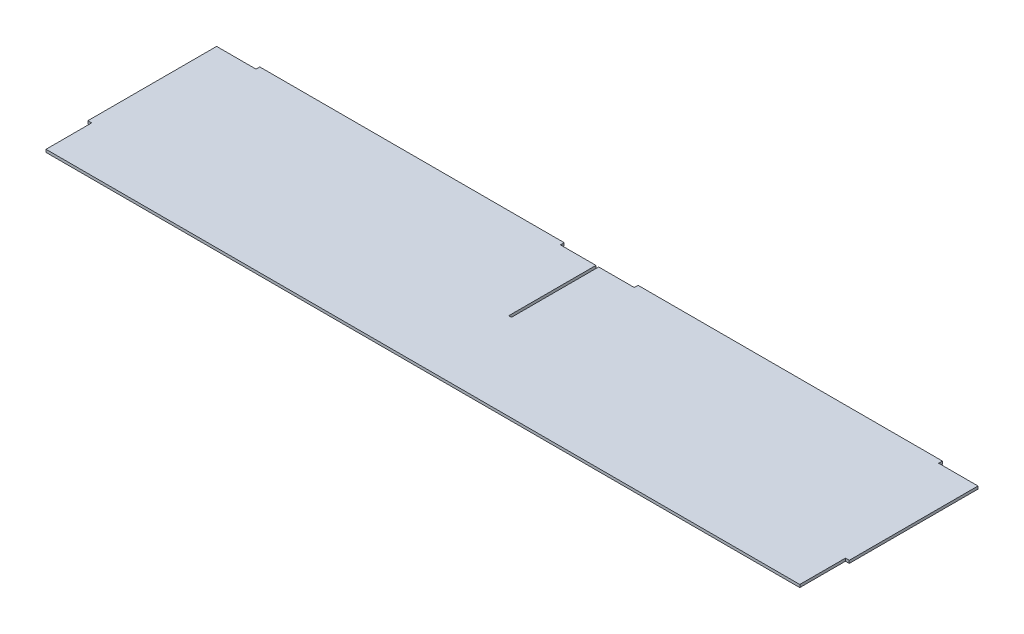
SolidWorks part; units mm, degrees
material "6061-T6 (SS)"
ref_plane "X-Y Datum" through (0, 0, 0) normal (0, 0, 1) x (1, 0, 0)
ref_plane "X-Z Datum" through (0, 0, 0) normal (0, 1, 0) x (1, 0, 0)
ref_plane "Y-Z Datum" through (0, 0, 0) normal (1, 0, 0) x (0, 0, -1)
sketch "Sketch1" plane through (0, 0, 0) normal (0, 1, 0) x (1, 0, 0)
  line L1 (-317.6778, 72.771) -> (317.6778, 72.771)
  line L2 (-317.6778, 72.771) -> (-317.6778, -72.771)
  line L3 (-317.6778, -72.771) -> (317.6778, -72.771)
  line L4 (317.6778, 72.771) -> (317.6778, -72.771)
  line L5 (-317.6778, 72.771) -> (317.6778, -72.771) construction
  line L6 (-317.6778, -72.771) -> (317.6778, 72.771) construction
  point P0 (0, 0)
  dimension "D1" = 635.3556
  dimension "D2" = 145.542
extrude "Boss-Extrude1" add sketch "Sketch1" along normal mid plane 2.286
sketch "Sketch2" plane through (0, 0, -72.771) normal (0, 0, -1) x (-1, 0, 0)
  line L0 (-317.6778, 1.143) -> (317.6778, 1.143) construction
  line L20 (-317.6778, -1.143) -> (317.6778, -1.143) construction
  line L21 (-284.8229, -1.143) -> (-30.8229, -1.143)
  line L22 (30.8229, -1.143) -> (284.8229, -1.143)
  line L40 (30.8229, -1.143) -> (30.8229, 1.143)
  line L41 (30.8229, 1.143) -> (284.8229, 1.143)
  line L42 (284.8229, 1.143) -> (284.8229, -1.143)
  line L56 (-284.8229, -1.143) -> (-284.8229, 1.143)
  line L57 (-284.8229, 1.143) -> (-30.8229, 1.143)
  line L58 (-30.8229, 1.143) -> (-30.8229, -1.143)
extrude "Boss-Extrude2" add sketch "Sketch2" along normal blind 3.175
sketch "Sketch3" plane through (0, -1.143, 0) normal (0, -1, 0) x (1, 0, 0)
  line L0 (-314.3758, 72.898) -> (-314.3758, 34.544)
  line L1 (-317.6778, 72.771) -> (-314.5028, 72.771)
  line L2 (-317.6778, 72.771) -> (-317.6778, 34.671)
  line L3 (-317.6778, 34.671) -> (-314.5028, 34.671)
  line L4 (-314.5028, 72.771) -> (-314.5028, 34.671)
  line L5 (-317.8048, 34.544) -> (-314.3758, 34.544)
  line L6 (-317.8048, 72.898) -> (-317.8048, 34.544)
  line L7 (-317.8048, 72.898) -> (-314.3758, 72.898)
  line M6 (317.6778, 72.771) -> (-317.6778, 72.771)
  line M7 (-317.6778, 72.771) -> (-317.6778, -72.771)
  dimension "D1" = 38.1
  dimension "D2" = 3.175
  dimension "D3" = 0.127
extrude "Cut-Extrude1" cut sketch "Sketch3" against normal through all contours L4 L3 M6 M7 region at (-316.0903, -1.143, 53.721)
mirror "Mirror1" about plane through (0, 0, 0) normal (1, 0, 0) of "Cut-Extrude1"
sketch "Sketch4" plane through (0, -1.143, 0) normal (0, -1, 0) x (1, 0, 0)
  line L0 (30.8229, -72.771) -> (-30.8229, -72.771) construction
  line L1 (-1.143, -72.771) -> (1.143, -72.771)
  line L2 (-1.143, -72.771) -> (-1.143, 0)
  line L3 (-1.143, 0) -> (1.143, 0)
  line L4 (1.143, -72.771) -> (1.143, 0)
  line L5 (-1.143, -75.946) -> (-1.143, -72.771) construction
  line L6 (1.3081, -72.9361) -> (1.3081, 0.1651)
  line L7 (-1.3081, 0.1651) -> (1.3081, 0.1651)
  line L8 (-1.3081, -72.9361) -> (-1.3081, 0.1651)
  line L9 (-1.3081, -72.9361) -> (1.3081, -72.9361)
  line M15 (-30.8229, -72.771) -> (30.8229, -72.771)
  dimension "D1" = 72.771
  dimension "D2" = 2.286
  dimension "D3" = 0.1651
extrude "Cut-Extrude2" cut sketch "Sketch4" against normal through all contours L4 L3 L2 M15 region at (0, -1.143, -36.3855)
